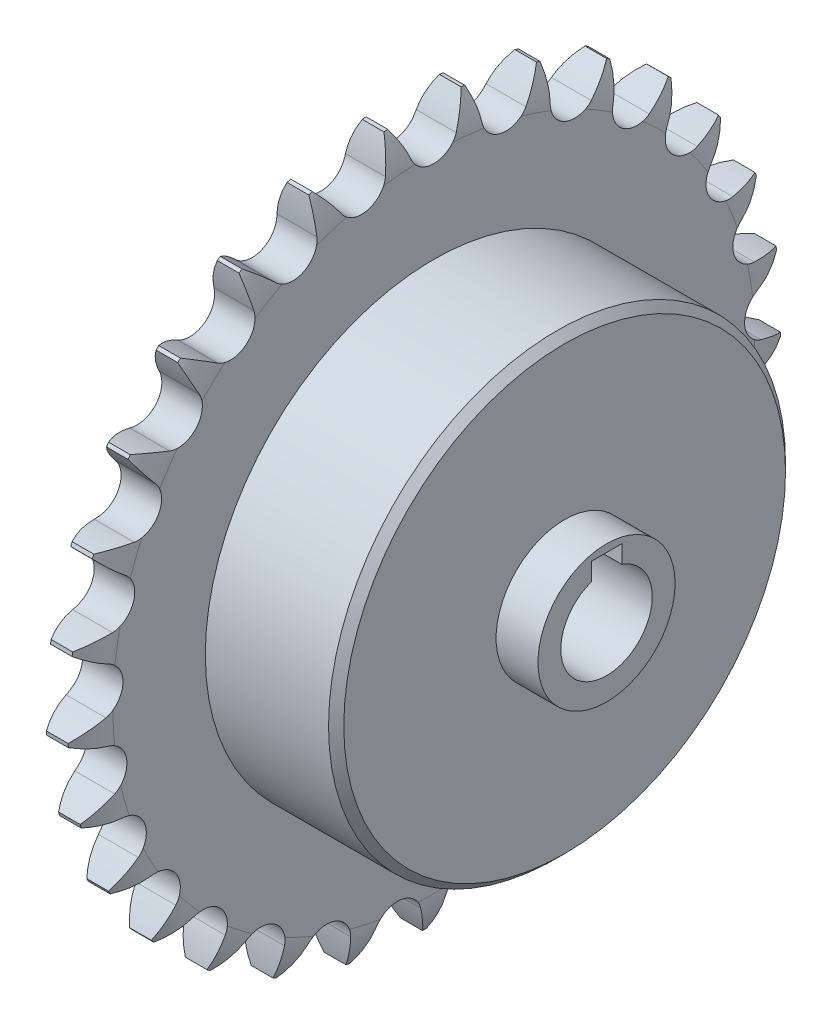
SolidWorks part; units mm, degrees
ref_plane "Plane1" through (0, 0, 0) normal (0, 0, 1) x (1, 0, 0)
ref_plane "Plane2" through (0, 0, 0) normal (0, 1, 0) x (1, 0, 0)
ref_plane "Plane3" through (0, 0, 0) normal (1, 0, 0) x (0, 0, -1)
sketch "Clipboard" plane through (0, 0, 0) normal (0, 1, 0) x (1, 0, 0)
  line L0 (0, 0) -> (8.3308, -4.6178)
  line L1 (-15, 0) -> (100, 0) construction
  line L2 (0, 0) -> (-0.8203, 0.9272)
  line L3 (0, 0) -> (-8.8973, 3.4006)
  line L4 (0, 0) -> (2.7113, 1.5029)
  line L5 (0, 0) -> (-46.8476, -17.4728)
  line L6 (0, 0) -> (-4.4098, -2.9753)
  line L7 (-0.8203, 0.9272) -> (42.4814, 25.9274)
  line L8 (-76.2, 38.1) -> (-73.4, 38.1)
  line L9 (-73.3242, 40.7328) -> (-72.926, 40.7699)
  line L10 (-73.4529, 9.1872) -> (-63.2129, 9.1872)
  circle A0 centre (0, 0) radius 3.175
  circle A1 centre (0, 0) radius 37.5
  circle A2 centre (0, 0) radius 37.5
  dimension "Num_teeth" = 29
  dimension "Thickness" = 5.3196
sketch "BasProSke" plane through (0, 0, 0) normal (0, 1, 0) x (1, 0, 0)
  line L0 (-10, 0) -> (60, 0) construction
  line L1 (0, 0) -> (0, 42.1309)
  line L2 (0, 0) -> (5.3196, 0)
  line L3 (5.3196, 0) -> (5.3196, 42.1309)
  line L4 (4.0816, 46.8268) -> (1.238, 46.8268)
  arc A0 (0, 42.1309) -> (1.238, 46.8268) centre (9.525, 42.1309) cw
  arc A1 (5.3196, 42.1309) -> (4.0816, 46.8268) centre (-4.2054, 42.1309) ccw
  dimension "D1" = 9.525
  dimension "Thickness" = 5.3196
  dimension "Diameter" = 93.6536
revolve "Base-Revolve" add sketch "BasProSke" angle 360 about L0
sketch "TooCutSke" plane through (0, 0, 0) normal (1, 0, 0) x (0, 0, -1)
  line L0 (0, 44.0804) -> (2.9826, 42.9025) construction
  line L1 (0, 0) -> (0, 107) construction
  line L2 (0, 44.0804) -> (-10, 44.0804) construction
  line L3 (0, 44.0804) -> (-2.9826, 42.9025) construction
  arc A0 (2.9826, 42.9025) -> (5.1154, 47.0495) centre (24.9531, 34.2251) cw
  arc A1 (2.9826, 42.9025) -> (-2.9826, 42.9025) centre (0, 44.0804) cw
  arc A2 (-2.9826, 42.9025) -> (-5.1154, 47.0495) centre (-24.9531, 34.2251) ccw
  arc A3 (5.1154, 47.0495) -> (-5.1154, 47.0495) centre (0, 0) ccw
extrude "ToothCut" cut sketch "TooCutSke" along normal through all
pattern_circular "TeethCuts" count 29 every 12.414 about axis through (-10, 0, 0) along (1, 0, 0) of "ToothCut"
sketch "HubNeaOneSke" plane through (0, 0, 0) normal (-1, 0, 0) x (0, 0, 1)
  circle A0 centre (0, 0) radius 37.5
  dimension "Diameter" = 75
extrude "HubNearOne" [suppressed] add sketch "HubNeaOneSke" along normal blind 44.6809
fillet "HubNearOneFillet" [suppressed] radius 0.4
sketch "HubNeaBotSke" plane through (0, 0, 0) normal (-1, 0, 0) x (0, 0, 1)
  circle A0 centre (0, 0) radius 37.5
  dimension "Diameter" = 75
extrude "HubNearBoth" [suppressed] add sketch "HubNeaBotSke" along normal blind 22.3405
fillet "HubNearBothFillet" [suppressed] radius 0.4
ref_plane "FarPln" through (5.3196, 0, 0) normal (1, 0, 0) x (0, 0, -1)
sketch "HubFarSke" plane through (5.3196, 0, 0) normal (1, 0, 0) x (0, 0, -1)
  circle A0 centre (0, 0) radius 37.5
  dimension "Diameter" = 75
extrude "HubFar" [suppressed] add sketch "HubFarSke" along normal blind 22.3405
fillet "HubFarFillet" [suppressed] radius 0.4
sketch "BorSke" plane through (0, 0, 0) normal (1, 0, 0) x (0, 0, -1)
  circle A0 centre (0, 0) radius 10
  dimension "Diameter" = 20
extrude "Bore" cut sketch "BorSke" along normal mid plane 100.001
sketch "KeySke" plane through (0, 0, 0) normal (1, 0, 0) x (0, 0, -1)
  line L0 (-3, 0) -> (-3, 12.8)
  line L1 (-3, 12.8) -> (3, 12.8)
  line L2 (3, 12.8) -> (3, 0)
  line L3 (0, 0) -> (0, 34) construction
  line L4 (-3, 0) -> (3, 0)
  dimension "Width" = 6
extrude "Keyway" [suppressed] cut sketch "KeySke" along normal mid plane 100.001
pattern_circular "Keyway2" [suppressed] count 2 every 90 about axis through (-10, 0, 0) along (1, 0, 0)
sketch "Sketch1" plane through (5.3196, 0, 0) normal (1, 0, 0) x (0, 0, -1)
  circle A0 centre (0, 0) radius 30
  circle A1 centre (0, 0) radius 6
  dimension "D1" = 60
  dimension "D2" = 12
extrude "Boss-Extrude1" add sketch "Sketch1" along normal offset from surface (24.6804 mm away) 30 up to face at (0, 0, -10)
sketch "Sketch2" plane through (5.3196, 0, 0) normal (-1, 0, 0) x (0, 0, 1)
  circle A0 centre (0, 0) radius 6 construction
  circle A1 centre (0, 0) radius 10
  circle A2 centre (0, 0) radius 10
  circle A3 centre (0, 0) radius 6
  dimension "D1" = 0
extrude "Boss-Extrude2" add sketch "Sketch2" along normal up to surface (5.3196 mm away) up to face at (0, 0, -10)
sketch "Sketch3" plane through (30, 0, 0) normal (1, 0, 0) x (0, 0, -1)
  line L0 (0, 0) -> (0, 6) construction
  line L1 (-2, 8) -> (2, 8)
  line L2 (-2, 8) -> (-2, 4)
  line L3 (-2, 4) -> (2, 4)
  line L4 (2, 8) -> (2, 4)
  line L5 (-2, 8) -> (2, 4) construction
  line L6 (-2, 4) -> (2, 8) construction
  circle A0 centre (0, 0) radius 6 construction
  point P0 (0, 6)
  dimension "D1" = 4
extrude "Cut-Extrude1" cut sketch "Sketch3" against normal through all
sketch "Sketch5" plane through (30, 0, 0) normal (1, 0, 0) x (0, 0, -1)
  circle A0 centre (0, 0) radius 9
  dimension "D1" = 18
extrude "Cut-Extrude3" cut sketch "Sketch5" against normal blind 7.5 flip side to cut
chamfer "Chamfer1" distance 1 angle 45 1 edges at (22.5, 0, -30)
sketch "Sketch6" plane through (30, 0, 0) normal (1, 0, 0) x (0, 0, -1)
  circle A0 centre (0, 0) radius 12.5215
extrude "Cut-Extrude4" cut sketch "Sketch6" against normal blind 2
equation "' \"Pitch@Clipboard\" = 12.7"
equation "' \"Num_strands@Clipboard\" = 1"
equation "' \"Num_teeth@Clipboard\" = 9"
equation "' \"Hub_dia@Clipboard\" = 50"
equation "' \"Overall_len@Clipboard\" = 3"
equation "' \"Diameter@BorSke\" = 12"
equation "' \"T_dim@Clipboard\" = 1"
equation "' \"Width@KeySke\" = 2"
equation "' \"Dr@Clipboard\" = 8.51"
equation "' \"Face_width@Clipboard\" = 7.2"
equation "' \"Side_radius@Clipboard\" = 12.7"
equation "' \"Side_relief@Clipboard\" = 1.27"
equation "' \"Transv_pitch@Clipboard\" = 13.92"
equation "' \"Show_teeth@Clipboard\" = 9"
equation "' \"Fillet_rad@Clipboard\" = 0.6"
equation "' \"Plate_wid@Clipboard\" = 11.8"
equation "\"Num_teeth@Clipboard\" = int( \"Num_teeth@Clipboard\" )"
equation "\"Num_teeth@Clipboard\" = ((sgn( \"Num_teeth@Clipboard\" - 5.0)+1)*( \"Num_teeth@Clipboard\" - 5.0))/2 +5.0"
equation "\"Num_teeth@Clipboard\" = ((sgn( \"Num_teeth@Clipboard\" - 200.0)-1)*( \"Num_teeth@Clipboard\" - 200.0))/-2 +200.0"
equation "\"MHD@Clipboard\" = \"Pitch@Clipboard\" * (1.0 / tan(3.14159265 / \"Num_teeth@Clipboard\" )) - 1.04 * \"Plate_wid@Clipboard\" - 0.76"
equation "\"Thickness@Clipboard\"  = \"Face_width@Clipboard\" + (\"Num_strands@Clipboard\" - 1) * \"Transv_pitch@Clipboard\""
equation "\"OAL@Clipboard\" = \"Thickness@Clipboard\" + 2 * \"Fillet_rad@Clipboard\" + 1"
equation "\"MHD@Clipboard\" = ((sgn( \"MHD@Clipboard\" - \"Hub_dia@Clipboard\" )-1)*( \"MHD@Clipboard\" - \"Hub_dia@Clipboard\" ))/-2+ \"Hub_dia@Clipboard\""
equation "\"OAL@Clipboard\" = ((sgn( \"OAL@Clipboard\" - \"Overall_len@Clipboard\" )+1)*( \"OAL@Clipboard\" - \"Overall_len@Clipboard\" ))/2 + \"Overall_len@Clipboard\" + 0.0005"
equation "\"Num_teeth@TeethCuts\" = int( \"Show_teeth@Clipboard\" ) + 1"
equation "\"Num_teeth@TeethCuts\" = ((sgn( \"Num_teeth@TeethCuts\" - \"Num_teeth@Clipboard\" )-1)*( \"Num_teeth@TeethCuts\" - \"Num_teeth@Clipboard\" ))/-2+ \"Num_teeth@Clipboard\""
equation "\"Num_teeth@TeethCuts\" = ((sgn( \"Num_teeth@TeethCuts\" - 2.0)+1)*( \"Num_teeth@TeethCuts\" - 2.0))/2 +2.0"
equation "\"Angle@TeethCuts\" = 360.0 / \"Num_teeth@Clipboard\""
equation "\"Seat_radius@TooCutSke\" = ( \"Pitch@Clipboard\" / 2.0) / sin(3.14159265 / \"Num_teeth@Clipboard\" ) - \"Dr@Clipboard\" / 2.0 + \"Dr@Clipboard\" * 0.505"
equation "\"R1@TooCutSke\"  = \"Dr@Clipboard\" * 0.505"
equation "\"X@TooCutSke\" = 140.0 - (90.0 / \"Num_teeth@Clipboard\")"
equation "\"R2@TooCutSke\" = 0.12 * \"Dr@Clipboard\" * ( \"Num_teeth@Clipboard\" + 2.0)"
equation "\"Overcut@TooCutSke\" = 0.5 + 0.625 * \"Pitch@Clipboard\" - 0.5 * \"Dr@Clipboard\"  +  \"Pitch@Clipboard\" / 2.0 / sin(3.14159265 / \"Num_teeth@Clipboard\" )"
equation "\"Diameter@BasProSke\" = 2.0 * ( 0.625 * \"Pitch@Clipboard\" - 0.5 * \"Dr@Clipboard\"  +  \"Pitch@Clipboard\" / 2.0 / sin(3.14159265 / \"Num_teeth@Clipboard\" ))"
equation "\"Thickness@BasProSke\"  = \"Thickness@Clipboard\""
equation "\"G1@BasProSke\" =  \"Side_relief@Clipboard\""
equation "\"G2@BasProSke\" =  \"Side_relief@Clipboard\""
equation "\"D1@BasProSke\" =  \"Side_radius@Clipboard\""
equation "\"Diameter@HubNeaOneSke\" = \"MHD@Clipboard\""
equation "\"Length@HubNearOne\" = \"OAL@Clipboard\" - \"Thickness@BasProSke\""
equation "\"Diameter@HubNeaBotSke\" = \"MHD@Clipboard\""
equation "\"Length@HubNearBoth\" = ( \"OAL@Clipboard\" - \"Thickness@BasProSke\" ) / 2.0"
equation "\"D1@HubNearOneFillet\" = \"Fillet_rad@Clipboard\""
equation "\"D1@HubNearBothFillet\" = \"Fillet_rad@Clipboard\""
equation "\"Thickness@FarPln\" = \"Thickness@BasProSke\""
equation "\"Diameter@HubFarSke\" = \"MHD@Clipboard\""
equation "\"Length@HubFar\" = ( \"OAL@Clipboard\" - \"Thickness@BasProSke\" ) / 2.0"
equation "\"D1@HubFarFillet\" = \"Fillet_rad@Clipboard\""
equation "\"D1@Bore\" = \"OAL@Clipboard\" * 2.0"
equation "\"D1@Keyway\" = \"OAL@Clipboard\" * 2.0"
equation "\"Offset@KeySke\" = \"T_dim@Clipboard\" + \"Diameter@BorSke\" / 2.0"
